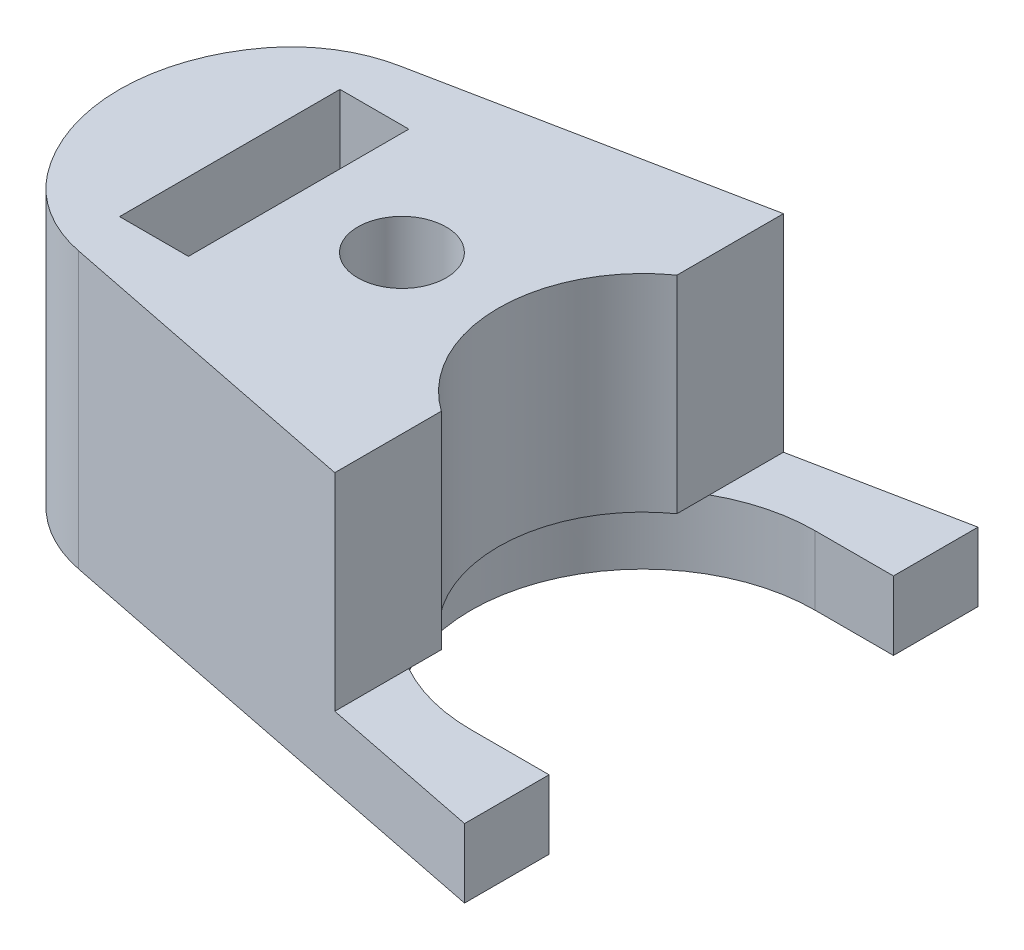
SolidWorks part; units mm, degrees
ref_plane "Front Plane" through (0, 0, 0) normal (0, 0, 1) x (1, 0, 0)
ref_plane "Top Plane" through (0, 0, 0) normal (0, 1, 0) x (1, 0, 0)
ref_plane "Right Plane" through (0, 0, 0) normal (1, 0, 0) x (0, 0, -1)
sketch "Sketch1" plane through (0, 0, 0) normal (0, 1, 0) x (1, 0, 0)
  line L0 (-0.1139, 1.9772) -> (-1.25, 1.7502)
  line L1 (-0.1139, -1.9772) -> (-1.25, -1.7502)
  line L2 (-0.6819, 1.25) -> (-0.6819, 0.8831)
  line L3 (-0.6819, -1.25) -> (-0.6819, -0.8831)
  line L4 (-1.25, -1.7502) -> (-4.1832, -1.1642)
  line L5 (-1.25, 1.7502) -> (-4.1832, 1.1642)
  line L6 (-1.859, 1.6286) -> (-1.859, -1.6286) construction
  line L7 (-1.25, 1.05) -> (-1.859, 1.05)
  line L8 (0, 1.6) -> (0, 1.3)
  line L9 (0, -1.3) -> (0, -1.6)
  line L10 (-1.25, 1.25) -> (-0.6819, 1.25)
  line L11 (-1.25, -1.25) -> (-0.6819, -1.25)
  line L12 (-0.6819, -1.25) -> (-0.6819, -1.8637)
  line L13 (-0.6819, 1.8637) -> (-0.6819, -1.8637) construction
  line L14 (-0.6819, 1.25) -> (-0.6819, 1.8637)
  line L15 (-1.859, 1.05) -> (-1.859, 1.6286)
  line L16 (-1.25, -1.05) -> (-1.859, -1.05)
  line L17 (-4.25, 0.8) -> (-3.75, 0.8)
  line L18 (-4.25, 0.8) -> (-4.25, -0.8)
  line L19 (-4.25, -0.8) -> (-3.75, -0.8)
  line L20 (-3.75, 0.8) -> (-3.75, -0.8)
  line L21 (-1.859, -1.05) -> (-1.859, -1.6286)
  line L22 (-1.859, 1.05) -> (-1.859, 0.8553)
  line L23 (-1.859, -1.05) -> (-1.859, -0.8553)
  circle A0 centre (-1.25, 0) radius 1.25
  circle A1 centre (-1.25, 0) radius 1.05
  arc A2 (0.1641, 1.9933) -> (0.1641, -1.9933) centre (0, 0) cw
  arc A3 (-0.1139, -1.9772) -> (0.1641, -1.9933) centre (0.0821, -0.9966) ccw
  arc A4 (-4.7783, 0.7954) -> (-4.7783, -0.7954) centre (-3.75, 0) ccw
  arc A5 (0.1641, 1.9933) -> (-0.1139, 1.9772) centre (0.0821, 0.9966) ccw
  arc A6 (-4.1832, 1.1642) -> (-4.7783, 0.7954) centre (-3.9873, 0.1835) ccw
  arc A7 (-4.1832, -1.1642) -> (-4.7783, -0.7954) centre (-3.9873, -0.1835) cw
  circle A8 centre (-3, 0) radius 0.3207
  circle A9 centre (0.5, 0) radius 0.3207
  arc A10 (0, 1.6) -> (0, -1.6) centre (0, 0) cw
  arc A11 (0, 1.3) -> (0, -1.3) centre (0, 0) cw
  point P12 (-3, 0)
  point P20 (0.5, 0)
extrude "Boss-Extrude2" add sketch "Sketch1" along normal blind 0.5 contours A7 L4 L21 A0 L15 L5 A6 A4 A8 L17 L20 L19 L18 | A0 L10 L14 L0 L5 L15 | A0 L21 L4 L1 L12 L11 region at (-1.2486, 0, -1.4875) region at (-3.3635, 0, 0) region at (-1.2486, 0, 1.4875)
extrude "Boss-Extrude3" add sketch "Sketch1<28>" along normal blind 1.5 from offset 0.5 contours A1 L22 L15 A0 L21 L23 | A7 L4 L21 A0 L15 L5 A6 A4 A8 L17 L20 L19 L18 region at (-3.3635, 0, 0) region at (-1.8818, 0, -1.0708)
sketch "Sketch1<28>" plane through (0, 0, 0) normal (0, 1, 0) x (1, 0, 0) same geometry as "Sketch1"
